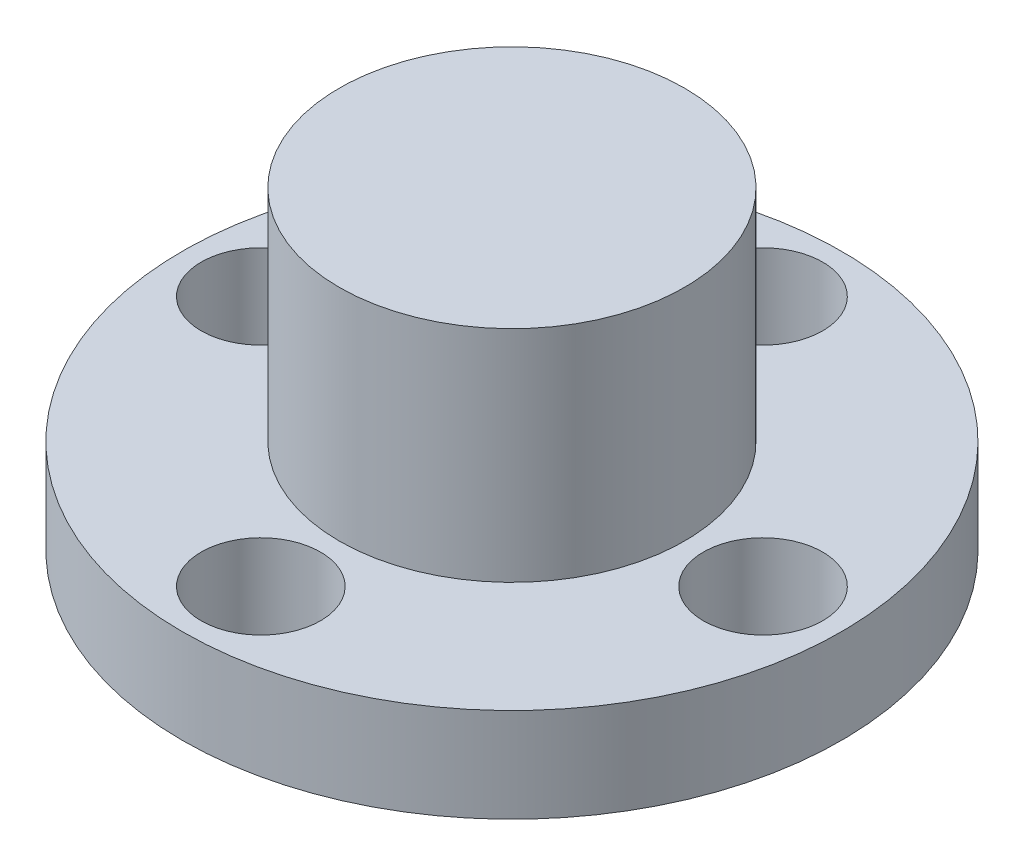
SolidWorks part; units mm, degrees
ref_plane "前视基准面" through (0, 0, 0) normal (0, 0, 1) x (1, 0, 0)
ref_plane "上视基准面" through (0, 0, 0) normal (0, 1, 0) x (1, 0, 0)
ref_plane "右视基准面" through (0, 0, 0) normal (1, 0, 0) x (0, 0, -1)
other "Configuration Table"
sketch "草图1" plane through (0, 0, 0) normal (0, 1, 0) x (1, 0, 0)
  line L0 (0, 0) -> (10.5, 0) construction
  circle A0 centre (0, 0) radius 10.5
  circle A2 centre (0, 0) radius 8 construction
  circle A3 centre (8, 0) radius 1.9
  circle A4 centre (0, -8) radius 1.9
  circle A5 centre (-8, 0) radius 1.9
  circle A6 centre (0, 8) radius 1.9
  circle A7 centre (0, 0) radius 5.5
  dimension "D1" = 21
  dimension "D2" = 16
  dimension "D3" = 11
  dimension "D4" = 3.8
  dimension "D5" = 4
extrude "凸台-拉伸1" add sketch "草图1" along normal blind 3 contours A0 A7 A6 A5 A4 A3 | A7 region at (-10.203, 0, 0) region at (0, 0, 0)
extrude "凸台-拉伸2" add sketch "草图1<3>" along normal blind 10 contours A7 region at (0, 0, 0)
sketch "草图1<3>" plane through (0, 0, 0) normal (0, 1, 0) x (1, 0, 0) same geometry as "草图1"
